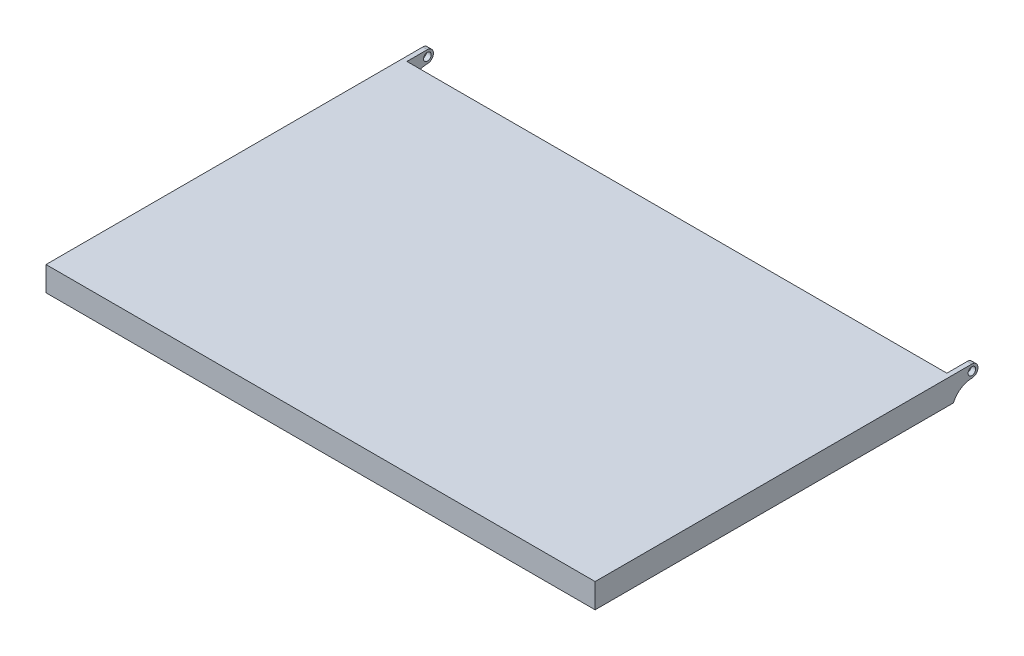
SolidWorks part; units mm, degrees
ref_plane "Alzado" through (0, 0, 0) normal (0, 0, 1) x (1, 0, 0)
ref_plane "Planta" through (0, 0, 0) normal (0, 1, 0) x (1, 0, 0)
ref_plane "Vista lateral" through (0, 0, 0) normal (1, 0, 0) x (0, 0, -1)
sketch "Croquis1" plane through (0, 0, 0) normal (0, 1, 0) x (1, 0, 0)
  line L0 (63.5, 63.5) -> (63.5, 390.652) construction
  line L1 (0, 0) -> (654.05, 0) construction
  line L2 (0, 0) -> (0, 454.152) construction
  line L3 (0, 454.152) -> (654.05, 454.152) construction
  line L4 (654.05, 0) -> (654.05, 454.152) construction
  line L5 (63.5, 390.652) -> (590.55, 390.652) construction
  line L6 (590.55, 63.5) -> (590.55, 390.652) construction
  line L7 (63.5, 63.5) -> (590.55, 63.5) construction
  line L8 (42.3333, 411.8187) -> (611.7167, 411.8187)
  line L9 (611.7167, 42.3333) -> (611.7167, 411.8187)
  line L10 (42.3333, 42.3333) -> (611.7167, 42.3333)
  line L11 (42.3333, 42.3333) -> (42.3333, 411.8187)
  dimension "D1" = 654.05
  dimension "D2" = 454.152
  dimension "D4" = 21.1667
  dimension "D5" = 42.3333
  dimension "D3" = 63.5
extrude "Saliente-Extruir1" add sketch "Croquis1" along normal blind 25.4
shell "Vaciado1" thickness 3.175 removed face at (327.025, 0, -227.076)
sketch "Croquis2" plane through (611.7167, 0, 0) normal (1, 0, 0) x (0, 0, -1)
  line L0 (411.8187, 25.4) -> (454.1487, 25.4) construction
  line L1 (454.1487, 25.4) -> (454.1487, 12.7) construction
  line L2 (454.1487, 12.7) -> (411.8187, 12.7) construction
  line L3 (411.8187, 25.4) -> (411.8187, 0) construction
  line L4 (432.9837, 25.4) -> (432.9837, 12.7) construction
  line L5 (411.8187, 0) -> (411.8187, 25.4)
  line L6 (411.8187, 25.4) -> (432.9837, 25.4)
  line L7 (439.3337, 0) -> (413.9337, 0) construction
  line L8 (439.3337, 19.05) -> (439.3337, 0) construction
  line L9 (411.8187, 0) -> (413.9337, 0)
  circle A0 centre (432.9837, 19.05) radius 3.9688
  arc A1 (432.9837, 12.7) -> (432.9837, 25.4) centre (432.9837, 19.05) ccw
  arc A3 (413.9337, 0) -> (432.9837, 12.7) centre (432.9837, -7.9375) cw
  dimension "D2" = 7.9375
  dimension "D4" = 2.115
  dimension "D1" = 42.33
  dimension "D3" = 25.4
extrude "Saliente-Extruir2" add sketch "Croquis2" against normal blind 4.7625
ref_plane "Plano1" through (327.025, 0, 0) normal (1, 0, 0) x (0, 0, -1)
mirror "Simetría1" about plane through (327.025, 0, 0) normal (1, 0, 0) of "Saliente-Extruir2"
